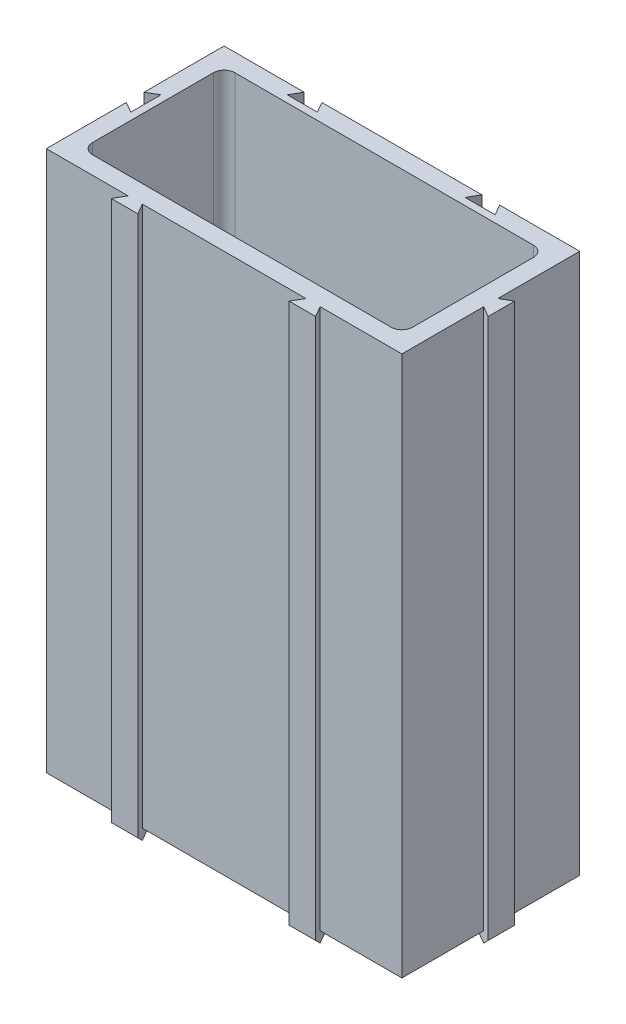
SolidWorks part; units mm, degrees
ref_plane "Front Plane" through (0, 0, 0) normal (0, 0, 1) x (1, 0, 0)
ref_plane "Top Plane" through (0, 0, 0) normal (0, 1, 0) x (1, 0, 0)
ref_plane "Right Plane" through (0, 0, 0) normal (1, 0, 0) x (0, 0, -1)
sketch "Sketch1" plane through (0, 0, 0) normal (0, 1, 0) x (1, 0, 0)
  line L0 (-11, 2.116) -> (-11, -2.116)
  line L3 (0, 16.0204) -> (0, -19.6084) construction
  line L5 (18.0663, 0) -> (-17.4129, 0) construction
  line L6 (-11, -2.116) -> (-12.5, -1.25)
  line L7 (-12.5, -1.25) -> (-12.5, -12.5)
  line L8 (-12.5, 1.25) -> (-12.5, 12.5)
  line L9 (-11, 2.116) -> (-12.5, 1.25)
  line L10 (0, 0) -> (-12.5, 12.5) construction
  line L11 (-2.116, 11) -> (-1.25, 12.5)
  line L12 (-1.25, 12.5) -> (-12.5, 12.5)
  line L13 (1.25, 12.5) -> (12.5, 12.5)
  line L14 (2.116, 11) -> (1.25, 12.5)
  line L15 (-2.116, 11) -> (2.116, 11)
  line L16 (-12.5, -12.5) -> (-1, -12.5)
  line L17 (-1, -12.5) -> (-1.866, -14)
  line L18 (-1.866, -14) -> (1.866, -14)
  line L19 (1, -12.5) -> (1.866, -14)
  line L20 (12.5, -12.5) -> (1, -12.5)
  line L21 (-16.0204, 0) -> (19.6084, 0) construction
  line L22 (12.5, -12.5) -> (12.5, -1) construction
  line L23 (12.5, -1) -> (14, -1.866) construction
  line L24 (14, 1.866) -> (14, -1.866) construction
  line L25 (12.5, 1) -> (14, 1.866) construction
  line L26 (12.5, 12.5) -> (12.5, 1) construction
  line L27 (-2.116, 21.0883) -> (-2.116, -12.7995) construction
  line L28 (1.25, 18.3402) -> (1.25, -13.7995) construction
  line L29 (-10, 10) -> (-10, -10)
  line L30 (-10, 10) -> (10, 10)
  line L31 (-10, -10) -> (10, -10)
  line L32 (10, 10) -> (10, -10) construction
  line L33 (22.884, 11) -> (23.75, 12.5)
  line L34 (26.25, 12.5) -> (37.5, 12.5)
  line L35 (27.116, 11) -> (26.25, 12.5)
  line L36 (22.884, 11) -> (27.116, 11)
  line L37 (24, -12.5) -> (23.134, -14)
  line L38 (23.134, -14) -> (26.866, -14)
  line L39 (26, -12.5) -> (26.866, -14)
  line L40 (37.5, -12.5) -> (26, -12.5)
  line L41 (37.5, -12.5) -> (37.5, -1)
  line L42 (37.5, -1) -> (39, -1.866)
  line L43 (39, 1.866) -> (39, -1.866)
  line L44 (37.5, 1) -> (39, 1.866)
  line L45 (37.5, 12.5) -> (37.5, 1)
  line L46 (35, 10) -> (35, -10)
  line L47 (15, -10) -> (35, -10)
  line L48 (15, 10) -> (35, 10)
  line L49 (23.75, 12.5) -> (12.5, 12.5)
  line L50 (12.5, -12.5) -> (24, -12.5)
  line L51 (35, 10) -> (15, -10) construction
  line L52 (15, 10) -> (10, 10)
  line L53 (15, -10) -> (10, -10)
  point P12 (-11, 0)
  point P13 (0, 11)
  point P23 (0, -14)
  point P31 (14, 0)
  point P39 (25, 0)
  point P40 (-10, 0)
  point P42 (0, -10)
  point P43 (0, 10)
  point P47 (25, 11)
  point P57 (25, -14)
  point P63 (39, 0)
  point P68 (25, -10)
  point P69 (25, 10)
  dimension "D1" = 60
  dimension "D2" = 2.5
  dimension "D3" = 25
  dimension "D4" = 1.5
  dimension "D5" = 45
  dimension "D6" = 0.5
  dimension "D7" = 60
  dimension "D8" = 0.5
  dimension "D9" = 20
  dimension "D10" = 2
  dimension "D11" = 25
extrude "Boss-Extrude1" add sketch "Sketch1" along normal blind 77.5 contours L20 L50 L37 L38 L39 L40 L41 L42 L43 L44 L45 L34 L35 L36 L33 L49 L13 L14 L15 L11 L12 L8 L9 L0 L6 L7 L16 L17 L18 L19 L47 L53 L31 L29 L30 L52 L48 L46 region at (-12.0396, 0, -2.1846)
sketch "Sketch2" plane through (0, 0, 0) normal (0, 1, 0) x (1, 0, 0)
  line L12 (35, -10) -> (35, 10)
  line L13 (-10, -10) -> (35, -10)
  line L14 (35, 10) -> (-10, 10)
  line L15 (-10, 10) -> (-10, -10)
  line L16 (35, -10) -> (35, 10)
  line L17 (-10, -10) -> (35, -10)
  line L18 (35, 10) -> (-10, 10)
  line L19 (-10, 10) -> (-10, -10)
  dimension "D1" = 0
extrude "Boss-Extrude2" add sketch "Sketch2" along normal blind 2.5
sketch "Sketch3" plane through (0, 2.5, 0) normal (0, 1, 0) x (1, 0, 0)
  line L0 (0, 14.7677) -> (0, 0) construction
  line L1 (0, 0) -> (-17.9797, 0) construction
  line L2 (0, 0) -> (-14.7542, 14.7542) construction
  line L3 (12.5, 10) -> (12.5, 0) construction
  line L4 (-10, 10) -> (35, 10) construction
  line L5 (12.5, 0) -> (52.9776, 0) construction
  circle A0 centre (-6, 6) radius 1.5
  circle A1 centre (6, 6) radius 1.5
  circle A2 centre (6, -6) radius 1.5
  circle A3 centre (-6, -6) radius 1.5
  circle A4 centre (31, -6) radius 1.5
  circle A5 centre (19, -6) radius 1.5
  circle A6 centre (19, 6) radius 1.5
  circle A7 centre (31, 6) radius 1.5
  dimension "D3" = 3
  dimension "D1" = 45
  dimension "D2" = 6
extrude "Cut-Extrude1" cut sketch "Sketch3" against normal through all both and the other way through all
chamfer "Chamfer3" distance 1.5 angle 45 16 edges at (-11, 0, 0) (0, 0, 14) (25, 0, 14) (39, 0, 0) (0, 0, -11) (25, 0, -11) (-6.875, 0, -12.5) (-12.5, 0, -6.875) (-12.5, 0, 6.875) (-6.75, 0, 12.5) (12.5, 0, 12.5) (37.5, 0, 6.75) (31.75, 0, 12.5) (37.5, 0, -6.75) (31.875, 0, -12.5) (12.5, 0, -12.5)
chamfer "Chamfer2" distance 1 angle 45 12 edges at (12.5, 2.5, 10) (-10, 2.5, 0) (12.5, 2.5, -10) (-6, 2.5, -4.5) (6, 2.5, -4.5) (6, 2.5, 7.5) (-6, 2.5, 7.5) (35, 2.5, 0) (31, 2.5, -4.5) (19, 2.5, -4.5) (19, 2.5, 7.5) (31, 2.5, 7.5)
fillet "Fillet1" radius 1.5 4 edges at (-10, 40.5, -10) (-10, 40.5, 10) (35, 40.5, 10) (35, 40.5, -10)
